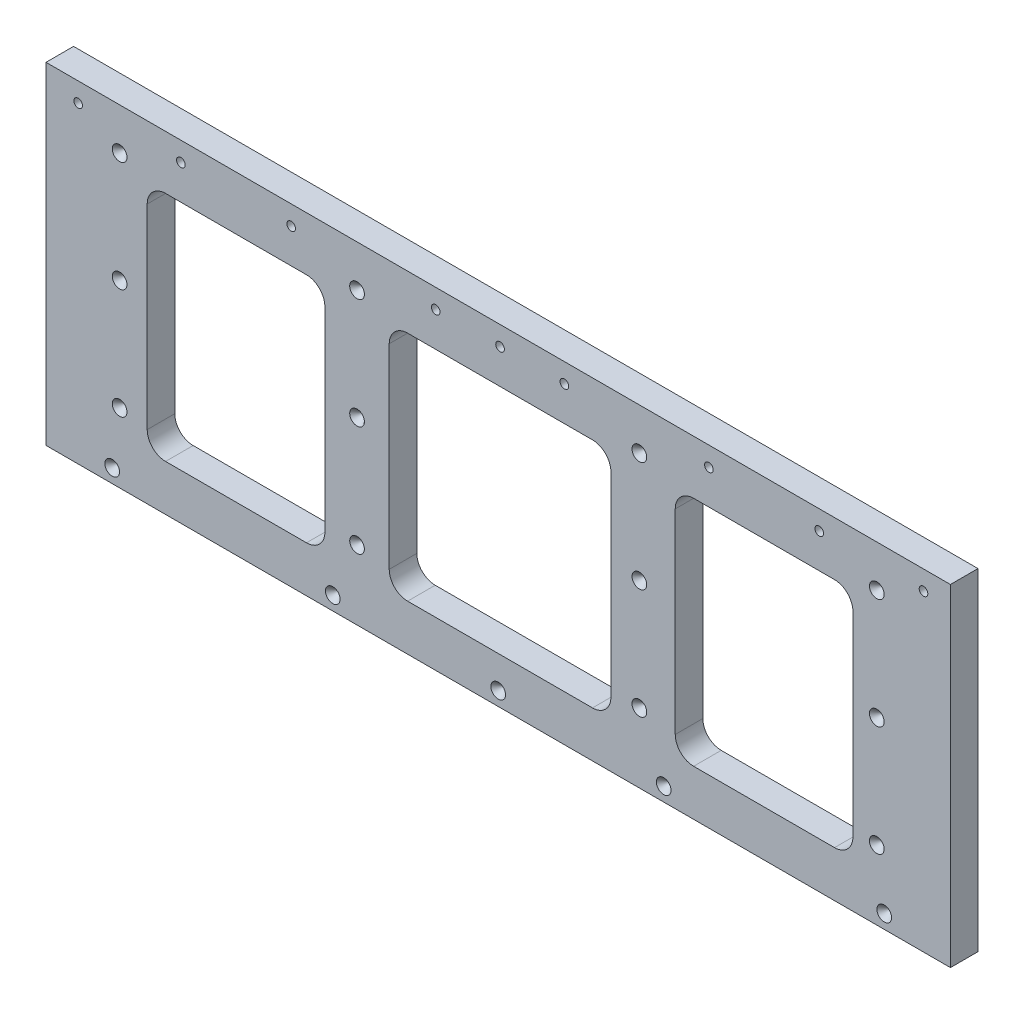
SolidWorks part; units mm, degrees
material "MDF"
ref_plane "Front Plane" through (0, 0, 0) normal (0, 0, 1) x (1, 0, 0)
ref_plane "Top Plane" through (0, 0, 0) normal (0, 1, 0) x (1, 0, 0)
ref_plane "Right Plane" through (0, 0, 0) normal (1, 0, 0) x (0, 0, -1)
sketch "Sketch1" plane through (0, 0, 0) normal (0, 0, 1) x (1, 0, 0)
  line L0 (128.7463, -697.8385) -> (128.7463, -132.715) construction
  line L1 (-496.0937, -132.715) -> (128.7463, -132.715)
  line L2 (-496.0937, -132.715) -> (-496.0937, -361.95)
  line L3 (-496.0937, -361.95) -> (128.7463, -361.95)
  line L4 (128.7463, -132.715) -> (128.7463, -361.95)
  line L5 (-496.0937, -132.715) -> (-496.0937, -697.8385) construction
  line L12 (128.7463, -132.715) -> (-84.6137, -132.715) construction
  line L13 (-290.722, -342.9) -> (-271.672, -342.9) construction
  dimension "D1" = 19.05
extrude "Boss-Extrude1" add sketch "Sketch1" along normal blind 19.05
hole_wizard "5/64 (0.07813) Diameter Hole1" positions "Sketch5" profile "Sketch6" hole size "5/64" standard "ANSI Inch"
sketch "Sketch5" plane through (-182.4037, -6471.4599, 19.05) normal (0, 0, 1) x (1, 0, 0)
  line L1 (-1.27, 6109.5099) -> (-1.27, 6338.7449) construction
  point P0 (-262.8265, 6157.4524)
  point P6 (-98.7933, 6157.4524)
  point P18 (-262.8265, 6233.6524)
  point P19 (-98.7933, 6233.6524)
  point P22 (-262.8265, 6309.8524)
  point P23 (-98.7933, 6309.8524)
  point P24 (-267.97, 6119.0349)
  point P34 (-115.57, 6119.0349)
  point P37 (-1.27, 6119.0349)
  point P40 (113.03, 6119.0349)
  point P44 (265.43, 6119.0349)
  point P55 (96.2533, 6309.8524)
  point P56 (260.2865, 6309.8524)
  point P59 (96.2533, 6233.6524)
  point P60 (260.2865, 6233.6524)
  point P63 (96.2533, 6157.4524)
  point P64 (260.2865, 6157.4524)
sketch "Sketch6" plane through (-445.2302, -314.0075, 19.05) normal (1, 0, 0) x (0, -1, 0)
  line L0 (0, 0) -> (0, 38.6962)
  line L1 (0, 38.6962) -> (0.9923, 38.1)
  line L2 (0.9923, 38.1) -> (0.9923, 4.7024)
  line L3 (0.9923, 4.7024) -> (5.08, 0)
  line L4 (5.08, 0) -> (0, 0)
  line L5 (-0.9923, 4.7024) -> (-5.08, 0) construction
  line L6 (0, 38.6962) -> (-0.9923, 38.1) construction
  line L7 (0, -6.35) -> (0, 107.95) construction
  dimension "Hole Dia." = 1.9845
  dimension "Hole Depth" = 38.1
  dimension "Near C'Sink Dia." = 10.16
  dimension "Near C'Sink Angle" = 82
  dimension "Drill Angle" = 118
hole_wizard "15/64 (0.23438) Diameter Hole1" positions "Sketch7" profile "Sketch8" hole size "15/64" standard "ANSI Inch" end condition up to next
sketch "Sketch7" plane through (0, 0, 0) normal (0, 0, -1) x (-1, 0, 0)
  point P0 (402.9075, -146.05)
  point P2 (326.7075, -146.05)
  point P4 (226.8537, -146.05)
  point P6 (182.4037, -146.05)
  point P8 (137.9537, -146.05)
  point P10 (38.1, -146.05)
  point P12 (-38.1, -146.05)
  point P13 (473.8687, -146.05)
  point P17 (-110.1471, -146.05)
sketch "Sketch8" plane through (-402.9075, -146.05, 0) normal (1, 0, 0) x (0, 1, 0)
  line L0 (0, 0) -> (0, 19.05)
  line L1 (0, 19.05) -> (2.9766, 19.05)
  line L2 (2.9766, 19.05) -> (2.9766, 0)
  line L5 (2.9766, 0) -> (0, 0)
  line L11 (0, -6.35) -> (0, 107.95) construction
  dimension "Thru Hole Dia." = 5.9533
  dimension "Thru Hole Depth" = 19.05
sketch "Sketch9" plane through (0, 0, 0) normal (0, 0, -1) x (-1, 0, 0)
  line L0 (0, -157.1498) -> (0, -342.9) construction
  line L1 (0, -250.0249) -> (93.1355, -250.0249) construction
  line L2 (61.3728, -330.2) -> (-61.3728, -330.2)
  line L3 (61.3728, -330.2) -> (61.3728, -169.8498)
  line L4 (61.3728, -169.8498) -> (-61.3728, -169.8498)
  line L5 (-61.3728, -330.2) -> (-61.3728, -169.8498)
  line L6 (61.3728, -330.2) -> (-61.3728, -169.8498) construction
  line L7 (61.3728, -169.8498) -> (-61.3728, -330.2) construction
  line L8 (93.1355, -250.0249) -> (271.672, -250.0249) construction
  line L9 (364.8075, -157.1625) -> (364.8075, -342.9) construction
  line L10 (258.972, -330.2) -> (105.8355, -330.2)
  line L11 (258.972, -330.2) -> (258.972, -169.8498)
  line L12 (258.972, -169.8498) -> (105.8355, -169.8498)
  line L13 (105.8355, -330.2) -> (105.8355, -169.8498)
  line L14 (258.972, -330.2) -> (105.8355, -169.8498) construction
  line L15 (258.972, -169.8498) -> (105.8355, -330.2) construction
  line L17 (426.1802, -330.2127) -> (303.4347, -330.2127)
  line L18 (426.1802, -330.2127) -> (426.1802, -169.8498)
  line L19 (426.1802, -169.8498) -> (303.4347, -169.8498)
  line L20 (303.4347, -330.2127) -> (303.4347, -169.8498)
  line L21 (426.1802, -330.2127) -> (303.4347, -169.8498) construction
  line L22 (426.1802, -169.8498) -> (303.4347, -330.2127) construction
  point P3 (0, -250.0249)
  point P8 (-74.0728, -342.9)
  point P13 (182.4037, -250.0249)
  point P20 (364.8075, -250.0313)
  dimension "D1" = 12.7
  dimension "D2" = 12.7
  dimension "D3" = 12.7
extrude "Cut-Extrude1" cut sketch "Sketch9" against normal up to next
fillet "Fillet1" radius 12.7 12 edges at (-303.4347, -330.2127, 9.525) (-303.4347, -169.8498, 9.525) (-426.1802, -169.8498, 9.525) (-426.1802, -330.2127, 9.525) (-258.972, -330.2, 9.525) (-258.972, -169.8498, 9.525) (-105.8355, -169.8498, 9.525) (-105.8355, -330.2, 9.525) (61.3728, -330.2, 9.525) (-61.3728, -330.2, 9.525) (-61.3728, -169.8498, 9.525) (61.3728, -169.8498, 9.525)
